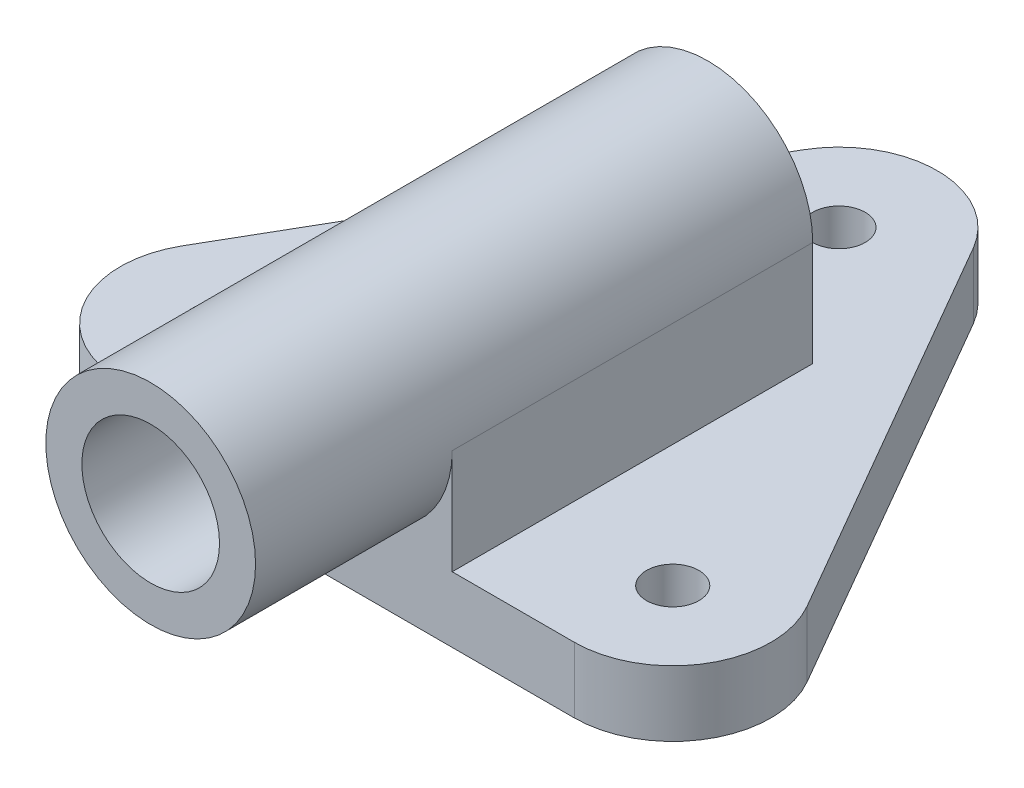
SolidWorks part; units mm, degrees
ref_plane "Front Plane" through (0, 0, 0) normal (0, 0, 1) x (1, 0, 0)
ref_plane "Top Plane" through (0, 0, 0) normal (0, 1, 0) x (1, 0, 0)
ref_plane "Right Plane" through (0, 0, 0) normal (1, 0, 0) x (0, 0, -1)
sketch "Sketch1" plane through (0, 0, 0) normal (0, 1, 0) x (1, 0, 0)
  line L0 (0, 25.0186) -> (0, -18.8647) construction
  line L1 (34.641, -60) -> (-34.641, -60) construction
  line L2 (12.9904, 7.5) -> (47.6314, -52.5)
  line L3 (34.641, -75) -> (-34.641, -75)
  line L4 (-47.6314, -52.5) -> (-12.9904, 7.5)
  line L5 (-10.8114, -20) -> (12.9904, -20) construction
  arc A0 (12.9904, 7.5) -> (-12.9904, 7.5) centre (0, 0) ccw
  circle A1 centre (0, 0) radius 4
  arc A2 (34.641, -75) -> (47.6314, -52.5) centre (34.641, -60) ccw
  circle A3 centre (34.641, -60) radius 4
  arc A4 (-47.6314, -52.5) -> (-34.641, -75) centre (-34.641, -60) ccw
  circle A5 centre (-34.641, -60) radius 4
  point P15 (0, -40)
  dimension "D1" = 30
  dimension "D2" = 8
  dimension "D4" = 60
  dimension "D5" = 55
  dimension "D3" = 3
extrude "Boss-Extrude1" add sketch "Sketch1" along normal blind 10
ref_plane "Plane1" through (0, 0, 20) normal (0, 0, 1) x (1, 0, 0)
sketch "Sketch2" plane through (0, 0, 20) normal (0, 0, 1) x (1, 0, 0)
  line L0 (16, 26) -> (16, 10)
  line L1 (16, 10) -> (-16, 10)
  line L2 (-16, 10) -> (-16, 26)
  line L3 (-34.641, 10) -> (34.641, 10) construction
  circle A0 centre (0, 26) radius 10.5
  circle A1 centre (0, 26) radius 16
  point P9 (0, 0)
  dimension "D1" = 32
  dimension "D2" = 21
extrude "Boss-Extrude3" add sketch "Sketch2" along normal blind 85 separate body contours A1 A0 region at (10.9937, 15.0063, 20)
extrude "Boss-Extrude4" add sketch "Sketch2<3>" along normal up to vertex (55 mm away) contours A1 L1 L0 | A1 L2 L1 region at (12.4261, 13.5739, 20) region at (-12.4261, 13.5739, 20) up to point (-34.641, 10, 75)
sketch "Sketch2<3>" plane through (0, 0, 20) normal (0, 0, 1) x (1, 0, 0) same geometry as "Sketch2"
